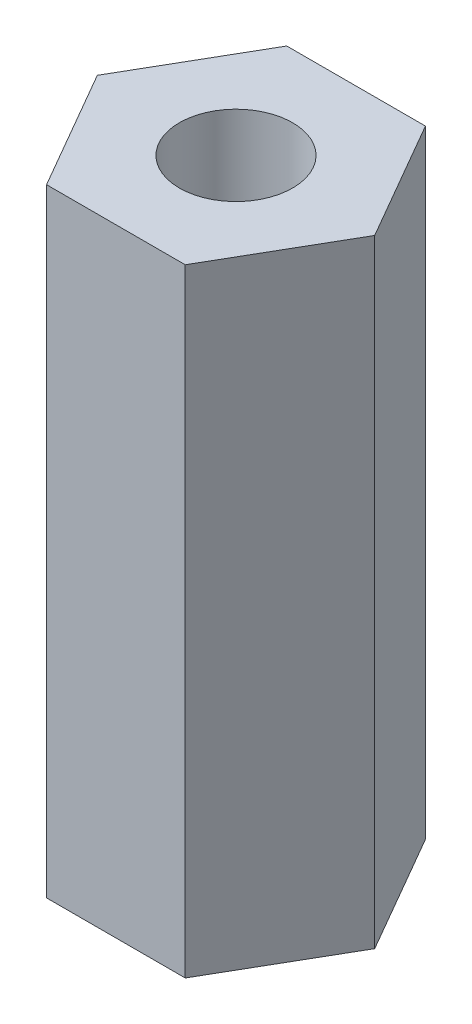
SolidWorks part; units mm, degrees
ref_plane "前视基准面" through (0, 0, 0) normal (0, 0, 1) x (1, 0, 0)
ref_plane "上视基准面" through (0, 0, 0) normal (0, 1, 0) x (1, 0, 0)
ref_plane "右视基准面" through (0, 0, 0) normal (1, 0, 0) x (0, 0, -1)
other "Configuration Table"
sketch "草图1" plane through (0, 0, 0) normal (0, 1, 0) x (1, 0, 0)
  line L1 (4.0415, 0) -> (2.0207, 3.5)
  line L2 (2.0207, 3.5) -> (-2.0207, 3.5)
  line L3 (-2.0207, 3.5) -> (-4.0415, 0)
  line L4 (-4.0415, 0) -> (-2.0207, -3.5)
  line L5 (-2.0207, -3.5) -> (2.0207, -3.5)
  line L6 (2.0207, -3.5) -> (4.0415, 0)
  circle A1 centre (0, 0) radius 1.65
  circle A2 centre (0, 0) radius 3.5 construction
  dimension "D1" = 7
  dimension "D2" = 3.3
extrude "凸台-拉伸2" add sketch "草图1" along normal blind 18
